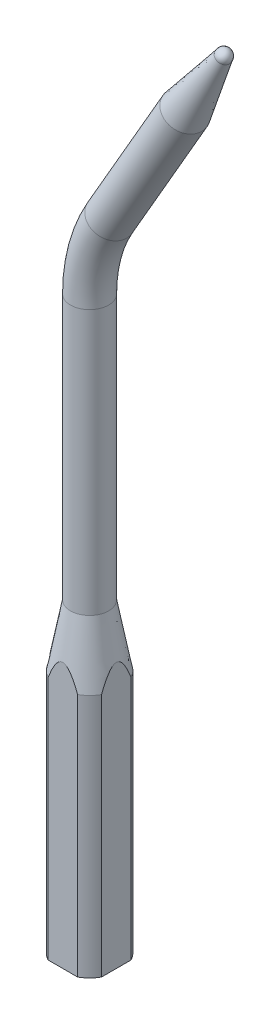
SolidWorks part; units mm, degrees
ref_plane "Front" through (0, 0, 0) normal (0, 0, 1) x (1, 0, 0)
ref_plane "Top" through (0, 0, 0) normal (0, 1, 0) x (1, 0, 0)
ref_plane "Right" through (0, 0, 0) normal (1, 0, 0) x (0, 0, -1)
sketch "草图1" plane through (0, 0, 0) normal (0, 0, 1) x (1, 0, 0)
  line L0 (0, 0) -> (0, 34.641)
  line L1 (2.6795, 44.641) -> (17.5, 70.3109)
  arc A0 (0, 34.641) -> (2.6795, 44.641) centre (20, 34.641) cw
  point P6 (0, 40)
  dimension "D4" = 20
  dimension "D1" = 40
  dimension "D2" = 35
  dimension "D3" = 150
sketch "草图2" plane through (0, 0, 0) normal (0, 1, 0) x (1, 0, 0)
  circle A0 centre (0, 0) radius 2.5
  dimension "D1" = 5
sweep "扫描1" add profiles "草图2" path "草图1"
sketch "草图3" plane through (0, 0, 0) normal (0, 0, 1) x (1, 0, 0)
  line L0 (0, 0) -> (0, -33.5139) construction
  line L1 (0, 0) -> (2.5, 0)
  line L2 (2.5, 0) -> (4, -8)
  line L3 (4, -8) -> (4, -40)
  line L4 (4, -40) -> (0, -40)
  line L5 (0, -40) -> (0, 0)
  dimension "D1" = 40
  dimension "D2" = 4
  dimension "D3" = 32
revolve "旋转1" add sketch "草图3" angle 360 about L0
chamfer "倒角1" distance 10 angle 9 1 edges at (17.5, 70.3109, 2.5) first distance on face at (17.5, 70.3109, 2.5)
sketch "草图4" plane through (0, -40, 0) normal (0, -1, 0) x (1, 0, 0)
  line L0 (6.7969, 2.8089) -> (6.7969, -2.85)
  line L1 (-2.8089, 6.7969) -> (2.85, 6.7969)
  line L2 (-2.8089, 6.7969) -> (-2.8089, 3.5)
  line L3 (-2.8089, 3.5) -> (2.85, 3.5)
  line L4 (2.85, 6.7969) -> (2.85, 3.5)
  line L5 (6.7969, 2.8089) -> (3.5, 2.8089)
  line L6 (3.5, 2.8089) -> (3.5, -2.85)
  line L7 (6.7969, -2.85) -> (3.5, -2.85)
  line L8 (2.8089, -6.7969) -> (-2.85, -6.7969)
  line L9 (2.8089, -6.7969) -> (2.8089, -3.5)
  line L10 (2.8089, -3.5) -> (-2.85, -3.5)
  line L11 (-2.85, -6.7969) -> (-2.85, -3.5)
  line L12 (-6.7969, -2.8089) -> (-6.7969, 2.85)
  line L13 (-6.7969, -2.8089) -> (-3.5, -2.8089)
  line L14 (-3.5, -2.8089) -> (-3.5, 2.85)
  line L15 (-6.7969, 2.85) -> (-3.5, 2.85)
  point P20 (0, 0)
  dimension "D1" = 3.5
  dimension "D2" = 4
extrude "切除-拉伸1" cut sketch "草图4" against normal blind 40
dome "圆顶1" faces to dome 1 distance 1 reverse direction no elliptical dome no face at (16.7066, 70.769, 0) parameters "D1"=1
